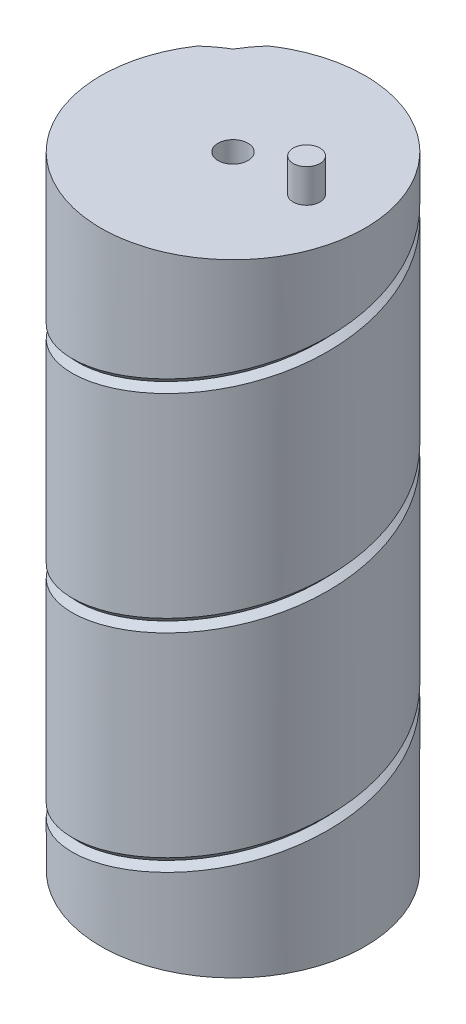
SolidWorks part; units mm, degrees
ref_plane "Front Plane" through (0, 0, 0) normal (0, 0, 1) x (1, 0, 0)
ref_plane "Top Plane" through (0, 0, 0) normal (0, 1, 0) x (1, 0, 0)
ref_plane "Right Plane" through (0, 0, 0) normal (1, 0, 0) x (0, 0, -1)
sketch "Sketch1" plane through (0, 0, 0) normal (0, 1, 0) x (1, 0, 0)
  line L0 (-19.75, 0) -> (19.75, 0) construction
  circle A0 centre (0, 0) radius 19.75
  dimension "D1" = 39.5
curve "Helix - Antenna Guide" pitch 31 height 93 radius 19.75 centre (0, 0, 0) axis (0, 1, 0) start towards (0, 0, 1)
extrude "Extrude - Main Body" add sketch "Sketch1<2>" along normal blind 93
sketch "Sketch1<2>" plane through (0, 0, 0) normal (0, 1, 0) x (1, 0, 0) same geometry as "Sketch1"
ref_point "Point2"
ref_point "Point1"
ref_plane "Plane1" through (-13.9654, 0, -13.9654) normal (-0.686, 0.2424, 0.686) x (-0.7276, -0.2285, -0.6468)
sketch "Sketch15" plane through (-13.9654, 0, -13.9654) normal (-0.686, 0.2424, 0.686) x (-0.7276, -0.2285, -0.6468)
  line L4 (0, 0) -> (0.2165, 0.8934)
  line L5 (0.2165, 0.8934) -> (-0.8934, 0.2165)
  line L8 (0, 0) -> (-0.2165, -0.8934)
  line L9 (-0.2165, -0.8934) -> (-0.8934, 0.2165)
  point P7 (-0.5549, -0.3384)
  dimension "D1" = 0.65
  dimension "D2" = 90
sweep "Cut - Antenna Wire Guide" cut profiles "Sketch15" path "Helix - Antenna Guide" align with end faces yes
sketch "Sketch23" plane through (0, 0, 0) normal (0, -1, 0) x (1, 0, 0)
  line L0 (-13.3154, -13.3154) -> (-8.3849, -14.1466)
  line L1 (-9.335, -17.4046) -> (-10.0329, -12.4535)
  arc A0 (-11.0473, -16.3713) -> (-16.3713, -11.0473) centre (0, 0) ccw construction
  arc A1 (-10.0329, -12.4535) -> (-8.3849, -14.1466) centre (-8.0525, -12.1744) cw
  arc A2 (-9.335, -17.4046) -> (-13.3154, -13.3154) centre (-14.1184, -18.0788) cw
  dimension "D2" = 2
  dimension "D1" = 2
  dimension "D3" = 5
  dimension "D4" = 5
ref_plane "Plane - Anchor Loop Exit" through (-9.335, 0, -17.4046) normal (-0.1396, 0, 0.9902) x (0.9902, 0, 0.1396)
ref_plane "Plane - Anchor Loop Peg" through (-10.0329, 0, -12.4535) normal (-0.1396, 0, 0.9902) x (0.9902, 0, 0.1396)
sketch "Sketch28" plane through (0, 93, 0) normal (0, 1, 0) x (1, 0, 0)
  circle A0 centre (11, 0) radius 2
  point P0 (0, 0)
  dimension "D1" = 4
  dimension "D2" = 11
extrude "Extruded Peg" add sketch "Sketch28" along normal blind 5
hole_wizard "Hole for Threaded Rod" positions "Sketch29" profile "Sketch30" hole size "#8" standard "ANSI Inch" end condition through all
sketch "Sketch29" plane through (0, 93, 0) normal (0, 1, 0) x (1, 0, 0)
  point P0 (0, 0)
sketch "Sketch30" plane through (0, 93, 0) normal (1, 0, 0) x (0, 0, 1)
  line L0 (0, 0) -> (0, 94.4693)
  line L1 (0, 94.4693) -> (2.2479, 94.4693)
  line L2 (2.2479, 94.4693) -> (2.2479, 0)
  line L5 (2.2479, 0) -> (0, 0)
  line L11 (0, -6.35) -> (0, 107.95) construction
  dimension "Thru Hole Dia." = 4.4958
  dimension "Thru Hole Depth" = 94.4693
sketch "Sketch31" plane through (0, 0, 0) normal (0, -1, 0) x (1, 0, 0)
  circle A0 centre (11, 0) radius 2.25
  dimension "D1" = 4.5
  dimension "D2" = 11
extrude "Cut Peg" cut sketch "Sketch31" against normal blind 5.5
sketch "Sketch32" plane through (0, 0, 0) normal (0, -1, 0) x (1, 0, 0)
  line L1 (2.1997, 3.81) -> (-2.1997, 3.81)
  line L2 (-2.1997, 3.81) -> (-4.3994, 0)
  line L3 (-4.3994, 0) -> (-2.1997, -3.81)
  line L4 (-2.1997, -3.81) -> (2.1997, -3.81)
  line L5 (2.1997, -3.81) -> (4.3994, 0)
  line L6 (4.3994, 0) -> (2.1997, 3.81)
  circle A0 centre (0, 0) radius 3.81 construction
  point P1 (-3.944, 2.441)
  dimension "D1" = 7.62
extrude "Cut-Extrude1" cut sketch "Sketch32" against normal blind 26.67
equation "\"pegD\"=10"
equation "\"pegHoleD\"=0.5"
equation "\"pegHoleOffset\"=0.5"
